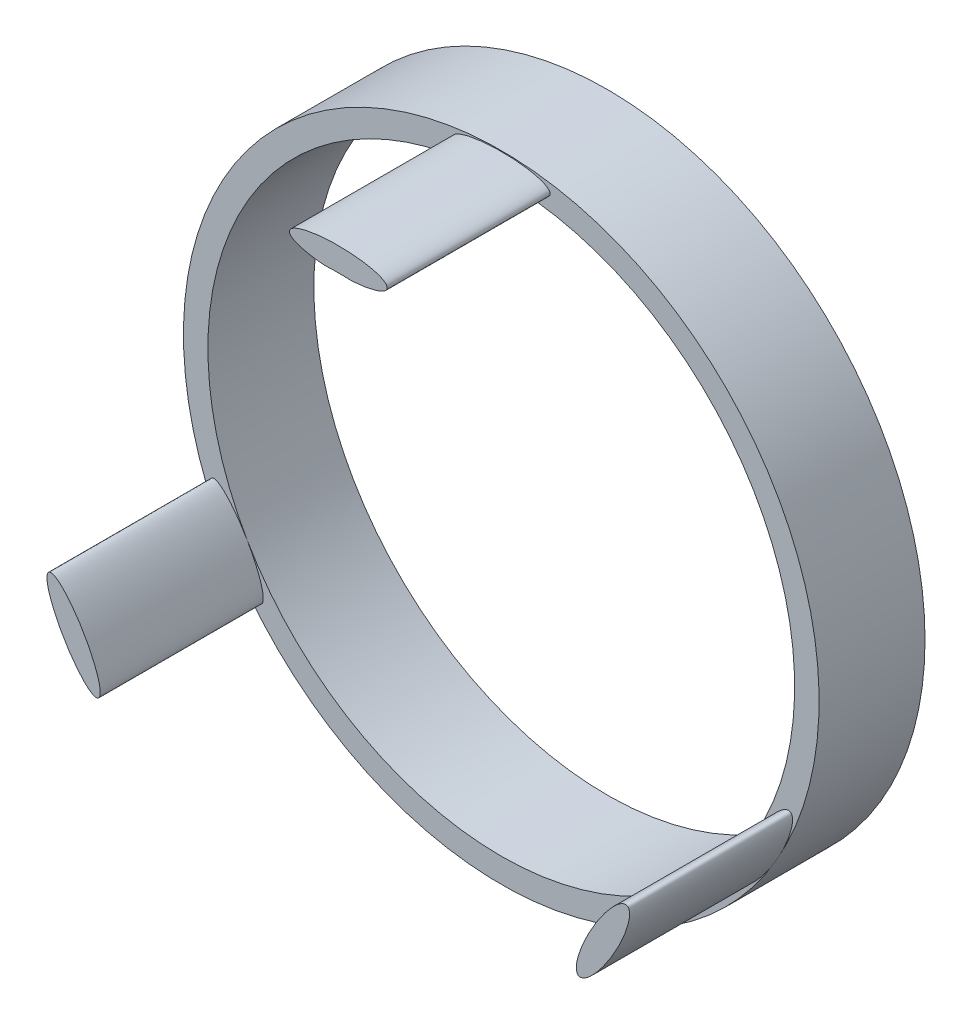
SolidWorks part; units mm, degrees
ref_plane "Front Plane" through (0, 0, 0) normal (0, 0, 1) x (1, 0, 0)
ref_plane "Top Plane" through (0, 0, 0) normal (0, 1, 0) x (1, 0, 0)
ref_plane "Right Plane" through (0, 0, 0) normal (1, 0, 0) x (0, 0, -1)
sketch "Sketch1" plane through (0, 0, 0) normal (0, 0, 1) x (1, 0, 0)
  circle A0 centre (0, 0) radius 19.5
  circle A1 centre (0, 0) radius 18
  dimension "D1" = 39
  dimension "D2" = 36
extrude "Boss-Extrude1" add sketch "Sketch1" along normal blind 6.5
sketch "Sketch2" plane through (0, 0, 6.5) normal (0, 0, 1) x (1, 0, 0)
  line L0 (0, 0) -> (-15.5885, -9) construction
  line L5 (0, 0) -> (0, 17.8977) construction
  line L6 (0, 17.8977) -> (0, 19.5)
  line L7 (0, -3.575) -> (0, 3.575) construction
  line L8 (0, 0) -> (15.5885, -9) construction
  line L9 (-15.5885, -9) -> (-16.8875, -9.75)
  line L10 (15.5885, -9) -> (16.8875, -9.75)
  ellipse E0 centre (0, 18.6989) end of major axis (3, 18.6989) minor radius 0.75
  ellipse E1 centre (-16.2403, -9.3709) end of major axis (-17.7403, -6.7728) minor radius 0.75
  ellipse E2 centre (16.238, -9.375) end of major axis (14.738, -11.9731) minor radius 0.75
  point P22 (0, 0)
  point P28 (0, 0)
  point P29 (0, 0)
  point P30 (7.7942, -4.5)
  circle M7 centre (0, 0) radius 18
extrude "Boss-Extrude2" add sketch "Sketch2" along normal blind 10 contours L6 E0 M7 | E0 L6 M7 | L9 E1 | L9 E1 | L10 E2 | L10 E2 region at (-16.8757, -8.2705, 6.5) region at (-1.2812, 18.7049, 6.5) region at (1.2812, 18.7049, 6.5) region at (16.8746, -8.2723, 6.5) region at (15.6014, -10.4777, 6.5) region at (-15.6024, -10.4758, 6.5)
